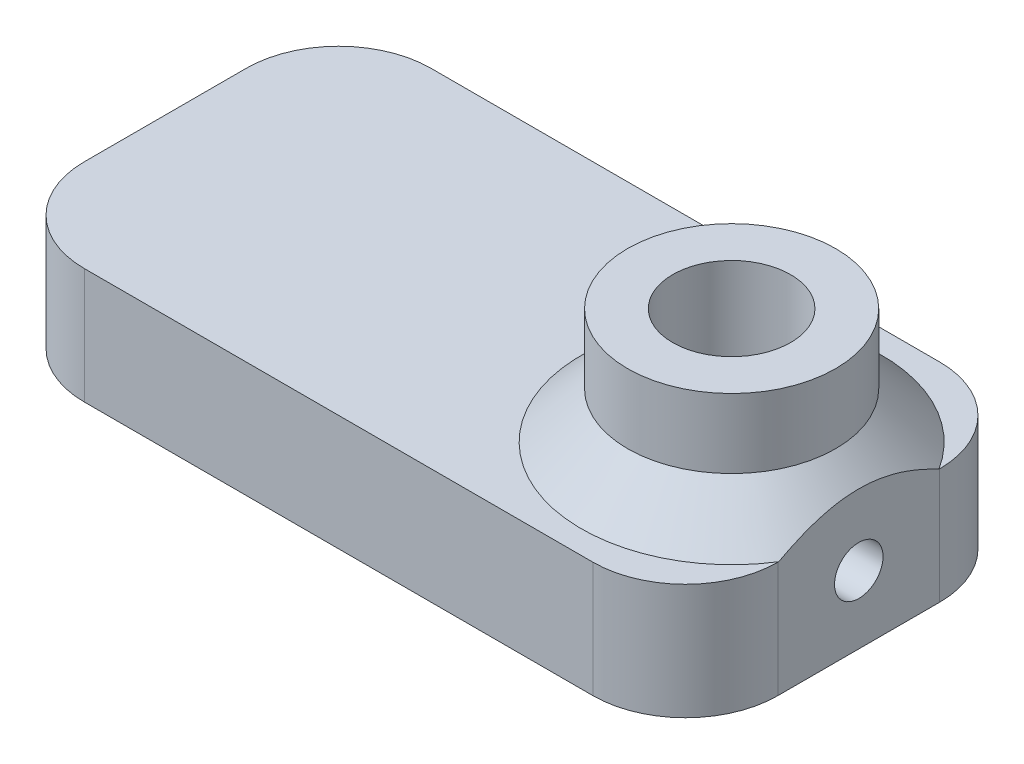
SolidWorks part; units mm, degrees
ref_plane "Front Plane" through (0, 0, 0) normal (0, 0, 1) x (1, 0, 0)
ref_plane "Top Plane" through (0, 0, 0) normal (0, 1, 0) x (1, 0, 0)
ref_plane "Right Plane" through (0, 0, 0) normal (1, 0, 0) x (0, 0, -1)
sketch "Sketch1" plane through (0, 0, 0) normal (0, 1, 0) x (1, 0, 0)
  line L1 (-49, 15) -> (11, 15)
  line L2 (-49, 15) -> (-49, -15)
  line L3 (-49, -15) -> (11, -15)
  line L4 (11, 15) -> (11, -15)
  circle A1 centre (0, 0) radius 9
  point P8 (11, 0)
  dimension "D2" = 18
  dimension "D3" = 30
  dimension "D4" = 60
  dimension "D1" = 11
extrude "Base" add sketch "Sketch1" along normal blind 10 contours L4 A1 L1 L2 L3 | A1 region at (-22.1283, 0, 0) region at (0, 0, 0)
fillet "AddALittleBeauty" radius 8 4 edges at (-49, 5, 15) (-49, 5, -15) (11, 5, -15) (11, 5, 15)
extrude "RodHolder" add sketch "Sketch1<3>" along normal blind 20 contours A1 region at (0, 0, 0)
sketch "Sketch1<3>" plane through (0, 0, 0) normal (0, 1, 0) x (1, 0, 0) same geometry as "Sketch1"
hole_wizard "M5x0.8 Tapped Hole for fixing rod" positions "Sketch3" profile "Sketch4" tap size "M5x0.8" standard "ANSI Metric"
sketch "Sketch3" plane through (11, 0, 0) normal (1, 0, 0) x (0, 0, -1)
  point P0 (0, 5.8799)
cosmetic thread "Hole Thread1" parameters "D1"=4.4624, "D2"=5
sketch "Sketch4" plane through (11, 5.8799, 0) normal (0, 1, 0) x (0, 0, -1)
  line L0 (0, 0) -> (0, 9.6618)
  line L1 (0, 9.6618) -> (2.1, 8.4)
  line L2 (2.1, 8.4) -> (2.1, 0)
  line L5 (2.1, 0) -> (0, 0)
  line L10 (0, 9.6618) -> (-2.1, 8.4) construction
  line L11 (0, -6.35) -> (0, 107.95) construction
  dimension "Tap Drill Dia." = 4.2
  dimension "Tap Drill Depth" = 8.4
  dimension "Drill Angle" = 118
chamfer "Chamfer1" distance 4 angle 45 1 edges at (0, 10, 9)
hole_wizard "Ø10.2 (10.2) Rod Hole" positions "Sketch5" profile "Sketch6" hole size "Ø10.2" standard "ANSI Metric" end condition through all
sketch "Sketch5" plane through (0, 20, 0) normal (0, 1, 0) x (1, 0, 0)
  point P0 (0, 0)
sketch "Sketch6" plane through (0, 20, 0) normal (1, 0, 0) x (0, 0, 1)
  line L0 (0, 0) -> (0, 20)
  line L1 (0, 20) -> (5.1, 20)
  line L2 (5.1, 20) -> (5.1, 0)
  line L5 (5.1, 0) -> (0, 0)
  line L11 (0, -6.35) -> (0, 107.95) construction
  dimension "Thru Hole Dia." = 10.2
  dimension "Thru Hole Depth" = 20
equation "\"D2@Sketch1\"=10.00mm+8"
